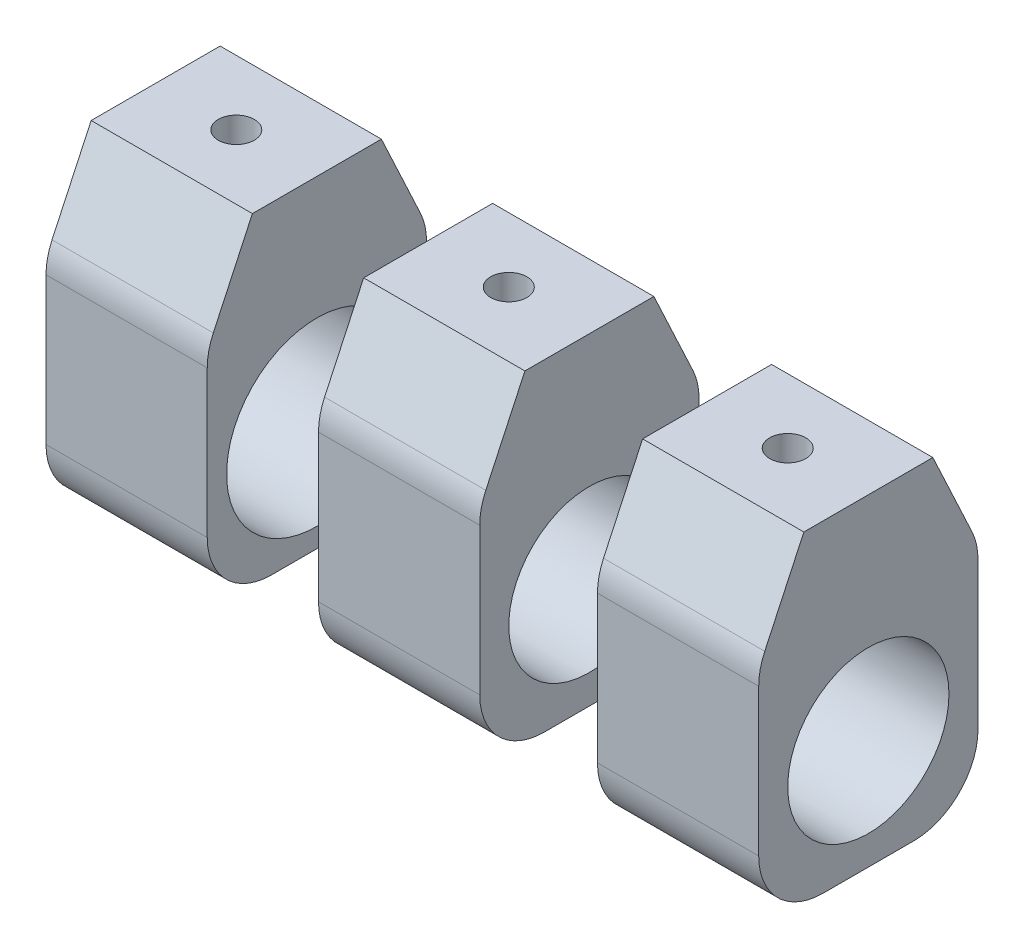
SolidWorks part; units mm, degrees
ref_plane "Front Plane" through (0, 0, 0) normal (0, 0, 1) x (1, 0, 0)
ref_plane "Top Plane" through (0, 0, 0) normal (0, 1, 0) x (1, 0, 0)
ref_plane "Right Plane" through (0, 0, 0) normal (1, 0, 0) x (0, 0, -1)
sketch "Sketch1" plane through (0, 0, 0) normal (1, 0, 0) x (0, 0, -1)
  line L0 (-10, 33) -> (10, 33)
  line L1 (10, 33) -> (17, 18)
  line L2 (17, 18) -> (17, -17)
  line L3 (17, -17) -> (-17, -17)
  line L4 (-17, -17) -> (-17, 18)
  line L5 (-17, 18) -> (-10, 33)
  circle A0 centre (0, 0) radius 14
  circle A1 centre (0, 0) radius 12.5
  point P6 (0, 33)
  dimension "D2" = 25
  dimension "D3" = 28
  dimension "D1" = 20
  dimension "D4" = 17
  dimension "D5" = 35
  dimension "D6" = 17
  dimension "D7" = 15
extrude "zoom lense mount" add sketch "Sketch1" along normal blind 25 contours L5 L4 L3 L2 L1 L0 A0 region at (0, 32.3954, 0)
extrude "spec mount1" add sketch "Sketch1<4>" along normal blind 25 from offset 42.25 separate body contours A0 A1 | L5 L4 L3 L2 L1 L0 A0 region at (0, 32.3954, 0) region at (0, 0, 13.604)
sketch "Sketch1<4>" plane through (0, 0, 0) normal (1, 0, 0) x (0, 0, -1) same geometry as "Sketch1"
extrude "spec mount 2" add sketch "Sketch1<5>" along normal blind 25 from offset 85.5 separate body contours L5 L4 L3 L2 L1 L0 A0 | A0 A1 region at (0, 32.3954, 0) region at (0, 0, 13.604)
sketch "Sketch1<5>" plane through (0, 0, 0) normal (1, 0, 0) x (0, 0, -1) same geometry as "Sketch1"
fillet "Fillet1" radius 10 4 edges at (12.5, -17, -17) (12.5, 18, -17) (12.5, -17, 17) (12.5, 18, 17)
fillet "Fillet2" radius 10 4 edges at (54.75, -17, -17) (54.75, 18, -17) (54.75, -17, 17) (54.75, 18, 17)
fillet "Fillet3" radius 10 4 edges at (98, -17, -17) (98, 18, -17) (98, -17, 17) (98, 18, 17)
sketch "Sketch2" plane through (0, 33, 0) normal (0, 1, 0) x (1, 0, 0)
  line L0 (85.5, -10) -> (85.5, 10) construction
  circle A0 centre (98, 0) radius 2.8
  dimension "D2" = 5.6
  dimension "D1" = 12.5
extrude "Cut-Extrude1" cut sketch "Sketch2" against normal blind 30
sketch "Sketch3" plane through (0, 33, 0) normal (0, 1, 0) x (1, 0, 0)
  line L0 (67.25, -10) -> (67.25, 10) construction
  circle A0 centre (54.75, 0) radius 2.8
  dimension "D2" = 5.6
  dimension "D1" = 12.5
extrude "Cut-Extrude2" cut sketch "Sketch3" against normal blind 30
sketch "Sketch4" plane through (0, 33, 0) normal (0, 1, 0) x (1, 0, 0)
  line L0 (0, -10) -> (0, 10) construction
  circle A0 centre (12.5, 0) radius 2.8
  dimension "D2" = 5.6
  dimension "D1" = 12.5
extrude "Cut-Extrude3" cut sketch "Sketch4" against normal blind 30
